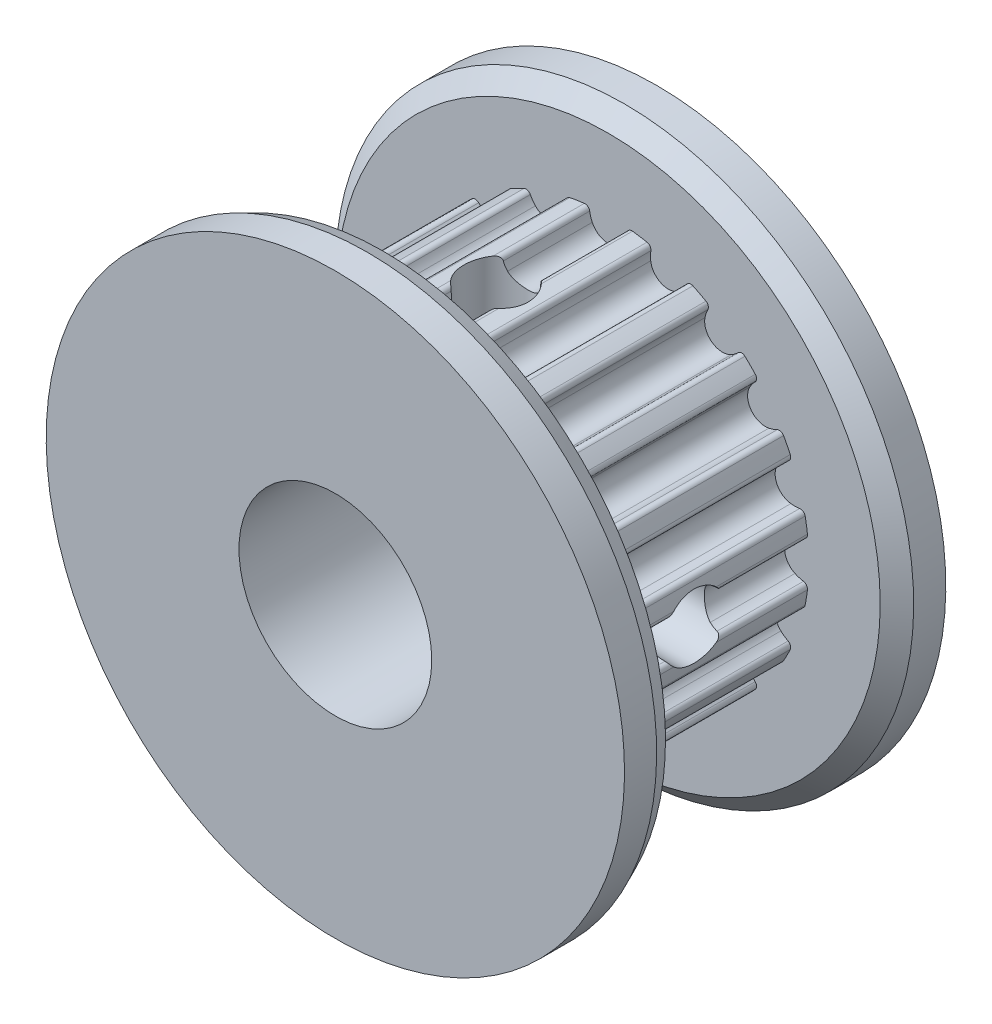
SolidWorks part; units mm, degrees
material "Aleación 6061"
ref_plane "Alzado" through (0, 0, 0) normal (0, 0, 1) x (1, 0, 0)
ref_plane "Planta" through (0, 0, 0) normal (0, 1, 0) x (1, 0, 0)
ref_plane "Vista lateral" through (0, 0, 0) normal (1, 0, 0) x (0, 0, -1)
sketch "Croquis1" plane through (0, 0, 0) normal (0, 0, 1) x (1, 0, 0)
  circle A0 centre (0, 0) radius 6.366
  dimension "D1" = 12.732
extrude "Saliente-Extruir1" add sketch "Croquis1" along normal blind 7
sketch "Croquis3" plane through (0, 0, 0) normal (0, 0, -1) x (-1, 0, 0)
  line L0 (0, 0) -> (0, 6.239) construction
  line L1 (0, 0) -> (0.976, 6.1622) construction
  line L2 (0.976, 6.1622) -> (0, 0) construction
  line L3 (0, 0) -> (-0.976, 6.1622) construction
  line L6 (0.976, 6.1622) -> (0.9959, 6.2876)
  line L8 (-0.976, 6.1622) -> (-0.9959, 6.2876)
  arc A0 (-0.7498, 6.1938) -> (-0.976, 6.1622) centre (0, 0) ccw
  arc A1 (-0.5037, 5.8059) -> (0.5037, 5.8059) centre (0, 6.039) ccw
  arc A2 (-0.5837, 6.0685) -> (-0.5037, 5.8059) centre (0.4038, 6.2259) ccw
  arc A3 (-0.5837, 6.0685) -> (-0.7498, 6.1938) centre (-0.7318, 6.0449) ccw
  arc A4 (0.5837, 6.0685) -> (0.5037, 5.8059) centre (-0.4038, 6.2259) cw
  arc A5 (0.5837, 6.0685) -> (0.7498, 6.1938) centre (0.7318, 6.0449) cw
  arc A6 (0.7498, 6.1938) -> (0.976, 6.1622) centre (0, 0) cw
  circle A7 centre (0, 0) radius 6.366 construction
  circle A11 centre (0, 0) radius 6.366
  circle M8 centre (0, 0) radius 6.366
  dimension "D1" = 6.239
  dimension "D4" = 1.11
  dimension "D5" = 2
  dimension "D7" = 0.3
  dimension "D3" = 18
  dimension "D6" = 0.2
extrude "Cortar-Extruir1" cut sketch "Croquis3" against normal through all contours A5 A6 L6 L8 A0 A3 A2 A1 A4 M8 region at (0, 6.0066, 0)
pattern_circular "MatrizC1" count 20 over 360 about axis through (0, 0, 7) along (0, 0, -1) of "Cortar-Extruir1"
sketch "Croquis5" plane through (0, 0, 0) normal (1, 0, 0) x (0, 0, -1)
  line L0 (0, 0) -> (1.5, 0)
  line L1 (0, -0.5037) -> (0, 0.5037) construction
  line L2 (1.5, 0) -> (1.5, 9)
  line L4 (0, 8.4583) -> (0, 0)
  line L5 (-7, 0) -> (-8.5, 0)
  line L6 (-7, 0.5037) -> (-7, -0.5037) construction
  line L7 (-8.5, 0) -> (-8.5, 9)
  line L10 (-7, 0) -> (-7, 8.776)
  line L11 (-8.5, 9) -> (-7.5, 9)
  line L12 (-7.5, 9) -> (-7, 8.776)
  line L13 (1.5, 9) -> (0.5, 9)
  line L14 (0.5, 9) -> (0, 8.4583)
  dimension "D1" = 9
  dimension "D2" = 1
  dimension "D3" = 9
  dimension "D4" = 0.5
  dimension "D5" = 1
  dimension "D6" = 0.5
revolve "Revolución1" add sketch "Croquis5" angle 360 about L5
sketch "Croquis6" plane through (0, 0, 8.5) normal (0, 0, 1) x (1, 0, 0)
  circle A0 centre (0, 0) radius 3
  dimension "D1" = 6
extrude "Cortar-Extruir2" cut sketch "Croquis6" against normal through all
sketch "Croquis7" plane through (0, 0, 0) normal (1, 0, 0) x (0, 0, -1)
  circle A0 centre (-3.5, 0) radius 1
  dimension "D1" = 2
extrude "Cortar-Extruir3" cut sketch "Croquis7" against normal through all both and the other way through all
sketch "Croquis8" plane through (0, 0, 0) normal (0, 1, 0) x (1, 0, 0)
  line L0 (0, 1.5) -> (0, -8.5) construction
  line L1 (9, 1.5) -> (-9, 1.5) construction
  line L2 (-3, -8.5) -> (3, -8.5) construction
  circle A1 centre (0, -3.5) radius 1
  dimension "D1" = 2
extrude "Cortar-Extruir4" cut sketch "Croquis8" against normal through all both and the other way through all
